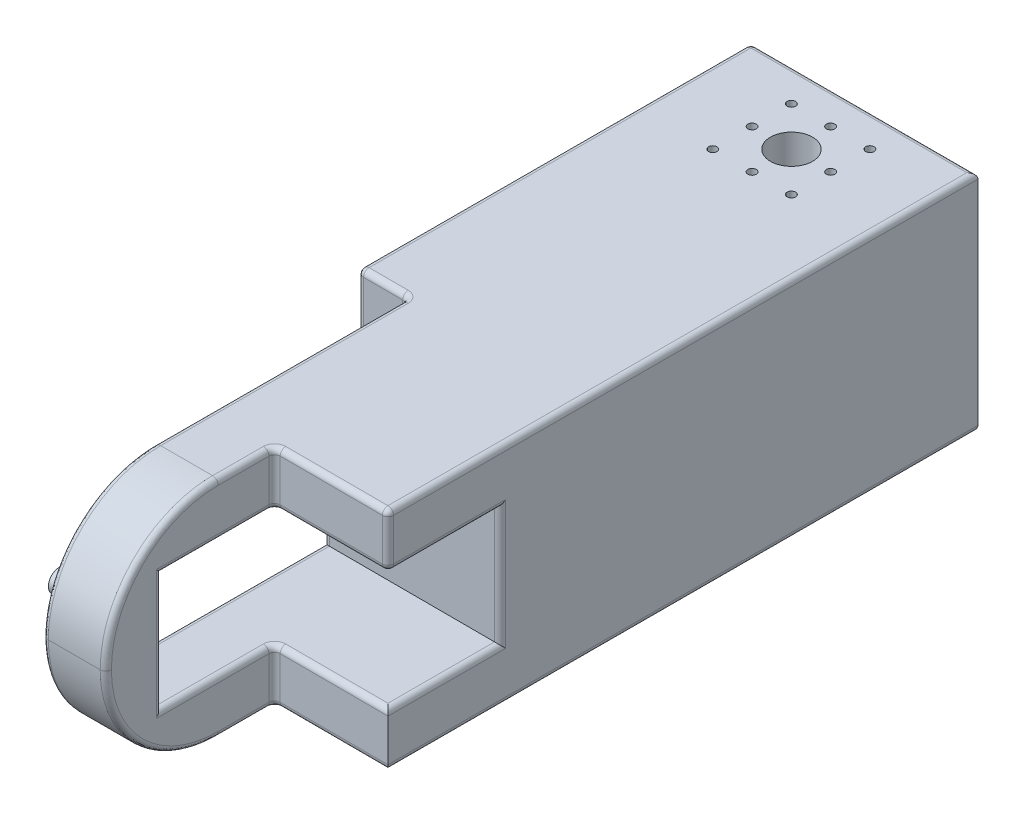
SolidWorks part; units mm, degrees
material "ABS"
ref_plane "Front Plane" through (0, 0, 0) normal (0, 0, 1) x (1, 0, 0)
ref_plane "Top Plane" through (0, 0, 0) normal (0, 1, 0) x (1, 0, 0)
ref_plane "Right Plane" through (0, 0, 0) normal (1, 0, 0) x (0, 0, -1)
sketch "Sketch4" plane through (0, 0, 0) normal (0, 1, 0) x (1, 0, 0)
  line L17 (-25.25, 20) -> (-5, 20)
  line L20 (-5, 20) -> (15.25, 20)
  line L21 (-25.5, -115) -> (-5.25, -115)
  line L22 (-5.25, -115) -> (15, -115)
  line L31 (15.25, 20) -> (15, -115)
  line L32 (-25.25, 20) -> (-25.5, -115)
extrude "MBODY" add sketch "Sketch4" along normal blind 40 contours L17 L20 L31 L22 L21 L32
sketch "Sketch5" plane through (0, 0, -20) normal (0, 0, -1) x (-1, 0, 0)
  line L3 (5, 15) -> (10, 15)
  line L4 (5, 15) -> (0, 15)
  line L5 (0, 15) -> (0, 25)
  line L6 (0, 25) -> (-10, 25)
  line L7 (-10, 25) -> (-10, 15)
  line L8 (10, 15) -> (10, 25)
  line L9 (10, 25) -> (20, 25)
  line L10 (20, 25) -> (20, 15)
  circle A1 centre (20, 15) radius 0.75
  circle A2 centre (20, 25) radius 0.75
  circle A3 centre (10, 25) radius 0.75
  circle A4 centre (10, 15) radius 0.75
  circle A5 centre (0, 15) radius 0.75
  circle A6 centre (0, 25) radius 0.75
  circle A7 centre (-10, 25) radius 0.75
  circle A8 centre (-10, 15) radius 0.75
extrude "FrontScrews" cut sketch "Sketch5" against normal blind 3 contours A8 | A7 | A6 | A5 | A4 | A3 | A1 | A2
sketch "Sketch7" plane through (0, 0, -20) normal (0, 0, -1) x (-1, 0, 0)
  circle A0 centre (5, 20) radius 2.75
extrude "GuideHole" add sketch "Sketch7" along normal blind 4 contours A0
sketch "Sketch10" plane through (-25.287, 0, -0.0352) normal (1, 0, 0.0019) x (0.0019, 0, -1)
  line L1 (-105, 20) -> (-105, 30.5)
  line L2 (-105, 20) -> (-105, 9.5)
  line L3 (-105, 30.5) -> (-65, 30.5)
  line L4 (-105, 9.5) -> (-65, 9.5)
  line L5 (-65, 9.5) -> (-65, 30.5)
extrude "ServoCut" cut sketch "Sketch10" along normal blind 40.5 contours L4 L5 L3 L1 L2
fillet "RoundEdge" radius 20 2 edges at (-5.25, 0, 115) (-5.25, 40, 115)
sketch "Sketch21" plane through (-20.213, 0, -2739.9977) normal (1, 0, 0.0019) x (0.0019, 0, -1)
  line L0 (-2889.9273, 40) -> (-2789.9273, 40)
  line L2 (-2889.9273, 40) -> (-2889.9273, 0)
  line L4 (-2789.9273, 40) -> (-2789.9273, 0)
  line L5 (-2789.9273, 0) -> (-2889.9273, 0)
  line L6 (-2719.9273, 40) -> (-2789.9273, 40)
  line L7 (-2719.9273, 40) -> (-2834.9275, 40) construction
  line M28 (-2720.0023, 0) -> (-2835.0025, 0)
  ellipse M29 centre (-2835.0025, 20) end of major axis (-2815.0025, 20) minor radius 20 (-2835.0025, 0) -> (-2855.0025, 20) cw
  ellipse M30 centre (-2835.0025, 20) end of major axis (-2855.0025, 20) minor radius 20 (-2855.0025, 20) -> (-2835.0025, 40) cw
  line M31 (-2835.0025, 40) -> (-2720.0023, 40)
  line M33 (-2844.9671, 30.5) -> (-2844.9671, 9.5)
  line M34 (-2844.9671, 9.5) -> (-2804.9671, 9.5)
  line M35 (-2804.9671, 9.5) -> (-2804.9671, 30.5)
  line M36 (-2804.9671, 30.5) -> (-2844.9671, 30.5)
extrude "TOPPUSHDOWN" cut sketch "Sketch21" along normal blind 9 contours L5 L2 L0 M29 M30 | M34 M33 M36 M35 | L4 M31 M28 M29 M30 M33 M34 M35 M36 region at (-25.4212, 39.2361, 72.4624) region at (-25.4444, 20, 84.9646) body kept at (-25.3795, 0, 49.9249)
sketch "Sketch12" plane through (-16.287, 0, -0.0005) normal (1, 0, 0.0019) x (0.0019, 0, -1)
  line L0 (-109.75, 15) -> (-105, 15)
  line L2 (-109.75, 25) -> (-109.75, 15)
  line L3 (-60.25, 15) -> (-60.25, 25)
  line L6 (-65, 25) -> (-60.25, 25)
  circle A0 centre (-109.75, 25) radius 2
  circle A1 centre (-109.75, 15) radius 2
  circle A2 centre (-60.25, 15) radius 2
  circle A3 centre (-60.25, 25) radius 2
extrude "SERVOHOLDERS" add sketch "Sketch12" against normal blind 2.25 contours A3 | A2 | A0 | A1
sketch "Sketch14" plane through (15.213, 0, 0.0023) normal (-1, 0, -0.0019) x (-0.0019, 0, 1)
  line L4 (120, 40) -> (120, 0)
  line L9 (120, 0) -> (85, 0)
  line L10 (85, 40) -> (85, 0)
  line L11 (85, 40) -> (120, 40)
extrude "CABLEACCESS" cut sketch "Sketch14" along normal blind 20.25 contours L10 L9 L4 L11
fillet "ROUNDEDGES" radius 1 36 edges at (-5.2037, 0, 89.9823) (-5.2037, 40, 89.9823) (-5.213, 9.5, 94.9834) (-5.213, 30.5, 94.9834) (-5.2315, 20, 105.0021) (-5.2392, 5.8579, 109.1421) (-5.2392, 34.1421, 109.1421) (-5, 40, -20) (-5, 0, -20) (4.9306, 9.5, 84.9834) (4.9306, 40, 84.9834) (4.9306, 30.5, 84.9834) (4.9306, 0, 84.9834) (-5.1944, 4.75, 84.9646) (-5.1944, 35.25, 84.9646) (15.1528, 40, 32.5011) (15.0556, 35.25, 85.0021) (15.074, 30.5, 75.0209) (15.0925, 20, 65.0397) (15.074, 9.5, 75.0209) (15.1528, 0, 32.5011) (-16.4891, 34.1421, 109.1421) (-16.4891, 5.8579, 109.1421) (-16.4212, 0, 72.4708) (-20.8795, 40, 49.9332) (-20.8795, 0, 49.9332) (-16.3795, 20, 49.9415) (-16.4212, 40, 72.4708) (-25.25, 20, -20) (-25.3147, 40, 14.9624) (-25.3795, 20, 49.9249) (-25.3147, 0, 14.9624) (-16.4814, 20, 104.9813) (-16.4444, 9.5, 84.9813) (-16.4074, 20, 64.9813) (-16.4444, 30.5, 84.9813)
sketch "Sketch8" plane through (-15, 0, 0) normal (0, 1, 0) x (0, 0, -1)
  line L0 (14, -2.9759) -> (14, -9.9759)
  line L2 (14, -2.9759) -> (7, -2.9759)
  line L3 (7, -2.9759) -> (0, -2.9759)
  line L4 (0, -2.9759) -> (0, -9.9759)
  line L6 (14, -16.9759) -> (7, -16.9759)
  line L7 (7, -16.9759) -> (0, -16.9759)
  line L8 (0, -16.9759) -> (0, -9.9759)
  line L11 (14, -9.9759) -> (14, -16.9759)
  circle A0 centre (0, -2.9759) radius 0.75
  circle A1 centre (7, -2.9759) radius 0.75
  circle A2 centre (14, -2.9759) radius 0.75
  circle A4 centre (14, -16.9759) radius 0.75
  circle A5 centre (7, -16.9759) radius 0.75
  circle A6 centre (0, -16.9759) radius 0.75
  circle A7 centre (0, -9.9759) radius 0.75
  circle A8 centre (14, -9.9759) radius 0.75
extrude "SideScrews1" cut sketch "Sketch8" along normal blind 3 contours A4 | A2 | A1 | A0 | A7 | A6 | A5 | A8
sketch "Sketch17" plane through (30, 40, 0) normal (0, -1, 0) x (-1, 0, 0)
  line L1 (28.0241, 7) -> (28.0241, 14)
  line L2 (28.0241, 14) -> (35.0241, 14)
  line L3 (35.0241, 14) -> (42.0241, 14)
  line L4 (42.0241, 14) -> (42.0241, 7)
  line L5 (42.0241, 7) -> (42.0241, -0.0049)
  line L6 (42.0241, -0.0049) -> (35.0241, -0.0049)
  line L7 (35.0241, -0.0049) -> (28.0241, -0.0049)
  line L8 (28.0241, -0.0049) -> (28.0241, 7)
  circle A0 centre (28.0241, 14) radius 0.75
  circle A1 centre (35.0241, 14) radius 0.75
  circle A2 centre (42.0241, 14) radius 0.75
  circle A3 centre (42.0241, 7) radius 0.75
  circle A4 centre (28.0241, 7) radius 0.75
  circle A5 centre (28.0241, -0.0049) radius 0.75
  circle A6 centre (35.0241, -0.0049) radius 0.75
  circle A7 centre (42.0241, -0.0049) radius 0.75
extrude "SideScrews2" cut sketch "Sketch17" along normal blind 3 contours A7 | A3 | A2 | A1 | A0 | A4 | A5 | A6
sketch "Sketch18" plane through (30, 0, 0) normal (0, 1, 0) x (-1, 0, 0)
  circle A0 centre (35, -7) radius 3.75
extrude "Cut-Extrude2" cut sketch "Sketch18" along normal blind 40 contours A0
sketch "Sketch22" plane through (-18.537, 0, -0.0343) normal (-1, 0, -0.0019) x (-0.0019, 0, 1)
  circle A0 centre (60.2797, 25) radius 0.75
  circle A1 centre (60.2797, 15) radius 0.75
  circle A2 centre (109.7797, 25) radius 0.75
  circle A3 centre (109.7797, 15) radius 0.75
extrude "Cut-Extrude4" cut sketch "Sketch22" against normal blind 3.25
